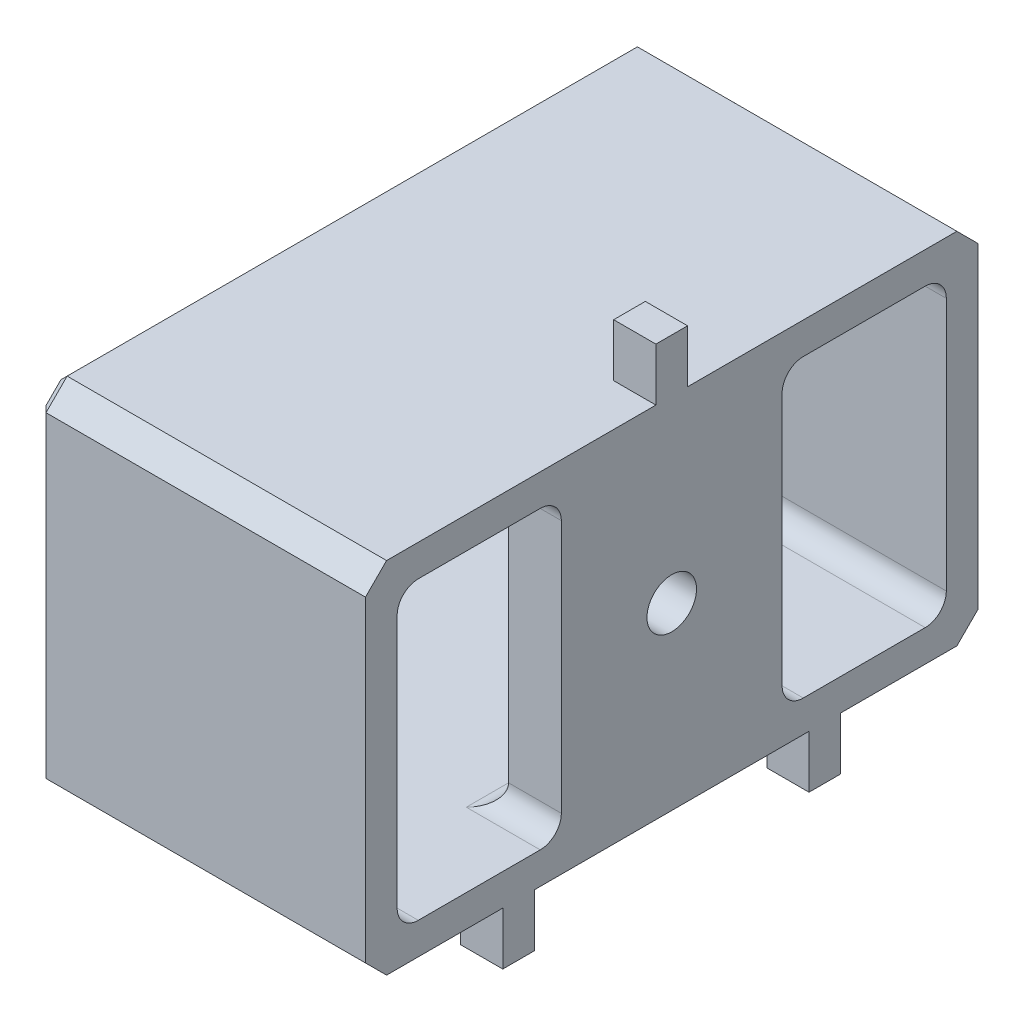
SolidWorks part; units mm, degrees
ref_plane "Front Plane" through (0, 0, 0) normal (0, 0, 1) x (1, 0, 0)
ref_plane "Top Plane" through (0, 0, 0) normal (0, 1, 0) x (1, 0, 0)
ref_plane "Right Plane" through (0, 0, 0) normal (1, 0, 0) x (0, 0, -1)
sketch "Sketch2" plane through (-2.794, 0, 0) normal (1, 0, 0) x (0, 0, -1)
  line L2 (-14.732, -58.674) -> (0, -58.674)
  line L3 (-14.732, -58.674) -> (-14.732, -67.31)
  line L4 (-14.732, -67.31) -> (0, -67.31)
  line L5 (0, -58.674) -> (0, -67.31)
  line L6 (-14.732, -58.674) -> (0, -67.31) construction
  line L7 (-14.732, -67.31) -> (0, -58.674) construction
  point P4 (-7.366, -62.992)
extrude "Extrude-Thin1" add sketch "Sketch2" along normal blind 7.9375 thin thin type one direction reverse wall 0.762
sketch "Sketch3" plane through (5.1435, 0, 0) normal (1, 0, 0) x (0, 0, -1)
  line L4 (-14.732, -58.674) -> (-14.732, -67.31)
  line L5 (-14.732, -67.31) -> (0, -67.31)
  line L6 (0, -67.31) -> (0, -58.674)
  line L7 (0, -58.674) -> (-14.732, -58.674)
  line L8 (-14.732, -58.674) -> (-14.732, -67.31)
  line L9 (-14.732, -67.31) -> (0, -67.31)
  line L10 (0, -67.31) -> (0, -58.674)
  line L11 (0, -58.674) -> (-14.732, -58.674)
  dimension "D1" = 0
extrude "Boss-Extrude1" add sketch "Sketch3" against normal blind 1.27
sketch "Sketch4" plane through (5.1435, 0, 0) normal (1, 0, 0) x (0, 0, -1)
  line L0 (-0.762, -66.548) -> (-4.711, -66.548)
  line L1 (-9.3446, -62.992) -> (-10.021, -62.992) construction
  line L2 (-10.021, -62.992) -> (-10.021, -61.2969) construction
  line L3 (-13.97, -59.436) -> (-10.021, -59.436)
  line L4 (-13.97, -59.436) -> (-13.97, -66.548)
  line L5 (-7.366, -58.674) -> (-7.366, -67.31) construction
  line L6 (0, -58.674) -> (-14.732, -58.674) construction
  line L7 (-14.732, -67.31) -> (0, -67.31) construction
  line L8 (-13.97, -66.548) -> (-10.021, -66.548)
  line L9 (-10.021, -59.436) -> (-10.021, -66.548)
  line L10 (-13.97, -59.436) -> (-10.021, -66.548) construction
  line L11 (-13.97, -66.548) -> (-10.021, -59.436) construction
  line L12 (-0.762, -59.436) -> (-0.762, -66.548)
  line L13 (-0.762, -59.436) -> (-4.711, -59.436)
  line L14 (-4.711, -59.436) -> (-4.711, -66.548)
  arc A0 (-10.021, -64.6783) -> (-10.021, -61.3057) centre (-11.7846, -62.992) ccw construction
  point P20 (-11.9955, -62.992)
extrude "Cut-Extrude1" cut sketch "Sketch4" against normal up to next
sketch "Sketch7" plane through (3.8735, 0, 0) normal (-1, 0, 0) x (0, 0, 1)
  line L0 (7.366, -59.436) -> (7.366, -62.992) construction
  line L1 (4.711, -59.436) -> (10.021, -59.436) construction
  line L2 (7.366, -62.992) -> (4.711, -62.992) construction
  line L3 (4.711, -66.548) -> (4.711, -59.436) construction
  circle A0 centre (7.366, -62.992) radius 1.016
  dimension "D1" = 2.032
extrude "Boss-Extrude2" add sketch "Sketch7" along normal blind 1.27
hole_wizard "#0-80 Tapped Hole1" positions "Sketch6" profile "Sketch5" tap size "#0-80" standard "ANSI Inch" end condition through all
sketch "Sketch6" plane through (5.1435, 0, 0) normal (1, 0, 0) x (0, 0, -1)
  point P0 (-7.366, -62.992)
sketch "Sketch5" plane through (5.1435, -62.992, 7.366) normal (0, 1, 0) x (0, 0, -1)
  line L0 (0, 0) -> (0, 7.9375)
  line L1 (0, 7.9375) -> (0.5956, 7.9375)
  line L2 (0.5956, 7.9375) -> (0.5956, 0)
  line L5 (0.5956, 0) -> (0, 0)
  line L11 (0, -6.35) -> (0, 107.95) construction
  dimension "Thru Tap Drill Dia." = 1.1913
  dimension "Thru Tap Drill Depth" = 7.9375
cosmetic thread "Hole Thread1" parameters "D2"=1.524
sketch "Sketch9" plane through (5.1435, 0, 0) normal (1, 0, 0) x (0, 0, -1)
  line L0 (-7.366, -58.674) -> (-7.366, -57.404)
  line L2 (-14.732, -67.31) -> (-7.366, -67.31) construction
  line L3 (-14.732, -67.31) -> (0, -67.31) construction
  line L4 (-7.366, -67.31) -> (0, -67.31) construction
  line L5 (-11.049, -67.31) -> (-11.049, -68.58)
  line L6 (-3.683, -67.31) -> (-3.683, -68.58)
  line L7 (0, -58.674) -> (-14.732, -58.674) construction
  dimension "D1" = 1.27
  dimension "D2" = 1.27
extrude "Extrude-Thin2" add sketch "Sketch9" against normal blind 1.27 thin thin type mid plane wall 0.762
fillet "Fillet1" radius 0.508 11 edges at (1.1748, -59.436, 13.97) (1.1748, -59.436, 0.762) (1.1748, -66.548, 0.762) (1.1748, -66.548, 13.97) (4.5085, -59.436, 4.711) (4.5085, -66.548, 4.711) (3.8735, -61.976, 7.366)
chamfer "Chamfer1" distance 0.508 angle 45 4 edges at (1.1748, -67.31, 14.732) (1.1748, -67.31, 0) (1.1748, -58.674, 0) (1.1748, -58.674, 14.732)
chamfer "Chamfer2" distance 0.254 angle 45 17 edges at (-2.794, -67.056, 14.478) (-2.794, -67.31, 7.366) (-2.794, -67.056, 0.254) (-2.794, -62.992, 0) (-2.794, -58.928, 0.254) (-2.794, -62.992, 14.732) (-2.794, -58.928, 14.478) (-2.794, -58.674, 7.366) (3.8735, -58.039, 6.985) (3.8735, -57.404, 7.366) (3.8735, -58.039, 7.747) (3.8735, -67.945, 10.668) (3.8735, -68.58, 11.049) (3.8735, -67.945, 11.43) (3.8735, -67.945, 3.302) (3.8735, -68.58, 3.683) (3.8735, -67.945, 4.064)
equation "\"D2@Sketch9\"=\"D1@Sketch9\""
